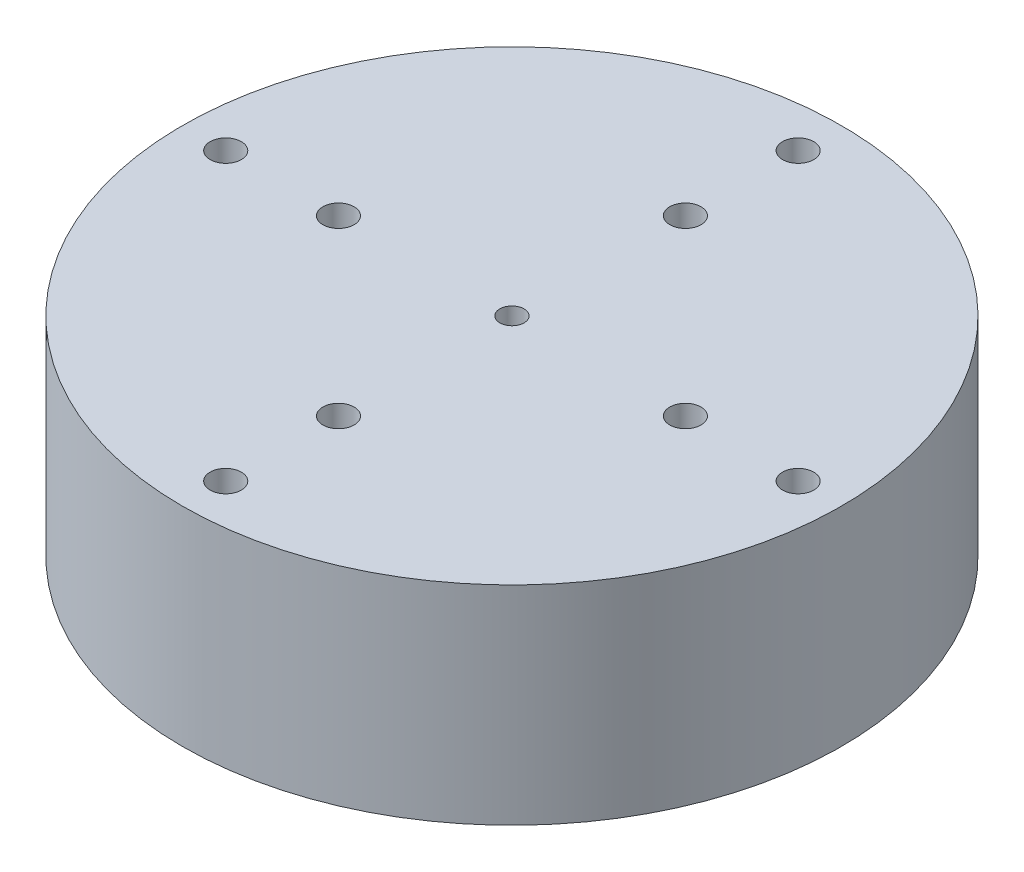
SolidWorks part; units mm, degrees
ref_plane "Front Plane" through (0, 0, 0) normal (0, 0, 1) x (1, 0, 0)
ref_plane "Top Plane" through (0, 0, 0) normal (0, 1, 0) x (1, 0, 0)
ref_plane "Right Plane" through (0, 0, 0) normal (1, 0, 0) x (0, 0, -1)
sketch "Sketch1" plane through (0, 0, 0) normal (0, 1, 0) x (1, 0, 0)
  circle A0 centre (0, 0) radius 47.5
  circle A1 centre (0, 0) radius 35
  dimension "D1" = 95
  dimension "D2" = 70
extrude "Boss-Extrude1" add sketch "Sketch1" along normal blind 30
sketch "Sketch2" plane through (0, 30, 0) normal (0, 1, 0) x (1, 0, 0)
  line L0 (-68.1724, 0) -> (77.449, 0) construction
  line L1 (0, 71.0864) -> (0, -90.573) construction
  circle A0 centre (0, 0) radius 35 construction
  circle A1 centre (0, 0) radius 47.5 construction
  circle A2 centre (0, 41.25) radius 2.25
  circle A3 centre (41.25, 0) radius 2.25
  circle A4 centre (0, -41.25) radius 2.25
  circle A5 centre (-41.25, 0) radius 2.25
  circle A6 centre (0, 25) radius 2.25
  circle A7 centre (25, 0) radius 2.25
  circle A8 centre (0, -25) radius 2.25
  circle A9 centre (-25, 0) radius 2.25
  point P5 (0, 35)
  point P6 (0, 47.5)
  point P9 (35, 0)
  point P12 (47.5, 0)
  dimension "D2" = 4.5
  dimension "D4" = 4.5
  dimension "D5" = 4.5
  dimension "D6" = 4.5
  dimension "D7" = 4.5
  dimension "D8" = 4.5
  dimension "D1" = 6.25
  dimension "D3" = 6.25
  dimension "D9" = 25
  dimension "D10" = 25
  dimension "D11" = 25
  dimension "D12" = 25
  dimension "D13" = 50
  dimension "D14" = 50
extrude "Cut-Extrude1" cut sketch "Sketch2" against normal through all
sketch "Sketch4" plane through (0, 30, 0) normal (0, 1, 0) x (1, 0, 0)
  circle A0 centre (0, 0) radius 35
extrude "Boss-Extrude2" add sketch "Sketch4" against normal blind 15
sketch "Sketch6" plane through (0, 30, 0) normal (0, 1, 0) x (1, 0, 0)
  circle A0 centre (0, 0) radius 1.75
  dimension "D1" = 3.5
extrude "Cut-Extrude2" cut sketch "Sketch6" against normal blind 30
extrude "Cut-Extrude3" cut sketch "Sketch2<2>" against normal through all
sketch "Sketch2<2>" plane through (0, 30, 0) normal (0, 1, 0) x (1, 0, 0) same geometry as "Sketch2"
